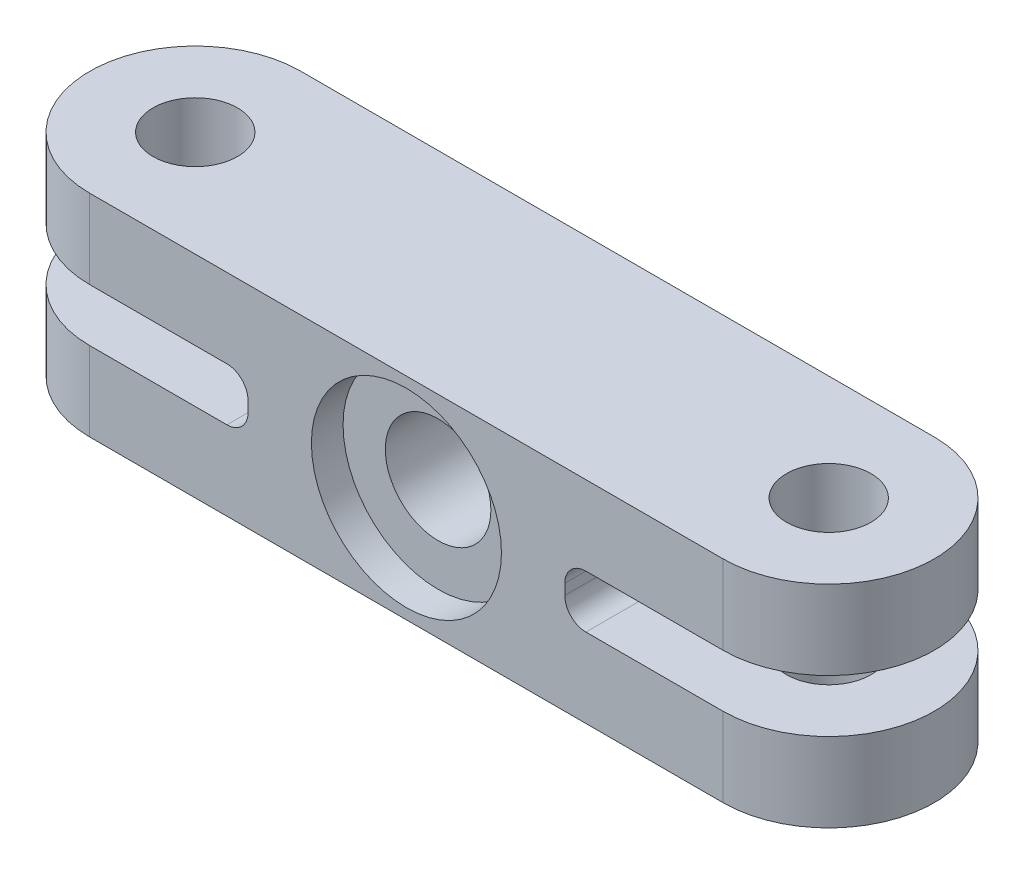
SolidWorks part; units mm, degrees
ref_plane "Front Plane" through (0, 0, 0) normal (0, 0, 1) x (1, 0, 0)
ref_plane "Top Plane" through (0, 0, 0) normal (0, 1, 0) x (1, 0, 0)
ref_plane "Right Plane" through (0, 0, 0) normal (1, 0, 0) x (0, 0, -1)
sketch "Sketch1" plane through (0, 0, 0) normal (0, 1, 0) x (1, 0, 0)
  line L1 (-30, -10) -> (30, -10)
  line L3 (-30, 10) -> (30, 10)
  line L5 (-30, -10) -> (30, 10) construction
  line L6 (-30, 10) -> (30, -10) construction
  arc A0 (-30, 10) -> (-30, -10) centre (-30, 0) ccw
  arc A1 (30, 10) -> (30, -10) centre (30, 0) cw
  circle A2 centre (-30, 0) radius 4
  circle A3 centre (30, 0) radius 4
  point P0 (0, 0)
  dimension "D3" = 8
  dimension "D1" = 60
  dimension "D2" = 20
extrude "Boss-Extrude1" add sketch "Sketch1" along normal blind 20
sketch "Sketch2" plane through (0, 0, 10) normal (0, 0, 1) x (1, 0, 0)
  line L0 (-40, 12.5) -> (-17, 12.5)
  line L2 (-15, 10.5) -> (-15, 9.5)
  line L3 (-17, 7.5) -> (-40, 7.5)
  line L4 (-40, 20) -> (-40, 0) construction
  line L5 (-40, 7.5) -> (-40, 12.5)
  line L6 (0, -11) -> (0, 11) construction
  line L7 (40, 7.5) -> (40, 12.5)
  line L8 (17, 7.5) -> (40, 7.5)
  line L9 (15, 10.5) -> (15, 9.5)
  line L10 (40, 12.5) -> (17, 12.5)
  arc A0 (17, 7.5) -> (15, 9.5) centre (17, 9.5) cw
  arc A1 (15, 10.5) -> (17, 12.5) centre (17, 10.5) cw
  arc A2 (-17, 7.5) -> (-15, 9.5) centre (-17, 9.5) ccw
  arc A3 (-15, 10.5) -> (-17, 12.5) centre (-17, 10.5) ccw
  point P0 (-15, 10)
  point P16 (15, 7.5)
  point P19 (15, 12.5)
  point P22 (-15, 7.5)
  point P25 (-15, 12.5)
  dimension "D4" = 2
  dimension "D1" = 25
  dimension "D2" = 5
  dimension "D3" = 10
extrude "Cut-Extrude1" cut sketch "Sketch2" against normal blind 20
sketch "Sketch3" plane through (0, 0, 10) normal (0, 0, 1) x (1, 0, 0)
  line L0 (-30, 0) -> (30, 0) construction
  circle A0 centre (0, 10) radius 9
  circle A1 centre (0, 10) radius 5
  dimension "D2" = 10
  dimension "D3" = 18
  dimension "D1" = 10
extrude "Cut-Extrude2" cut sketch "Sketch3" against normal blind 20 contours A1
extrude "Cut-Extrude3" cut sketch "Sketch3<3>" against normal blind 3 contours A0
sketch "Sketch3<3>" plane through (0, 0, 10) normal (0, 0, 1) x (1, 0, 0) same geometry as "Sketch3"
